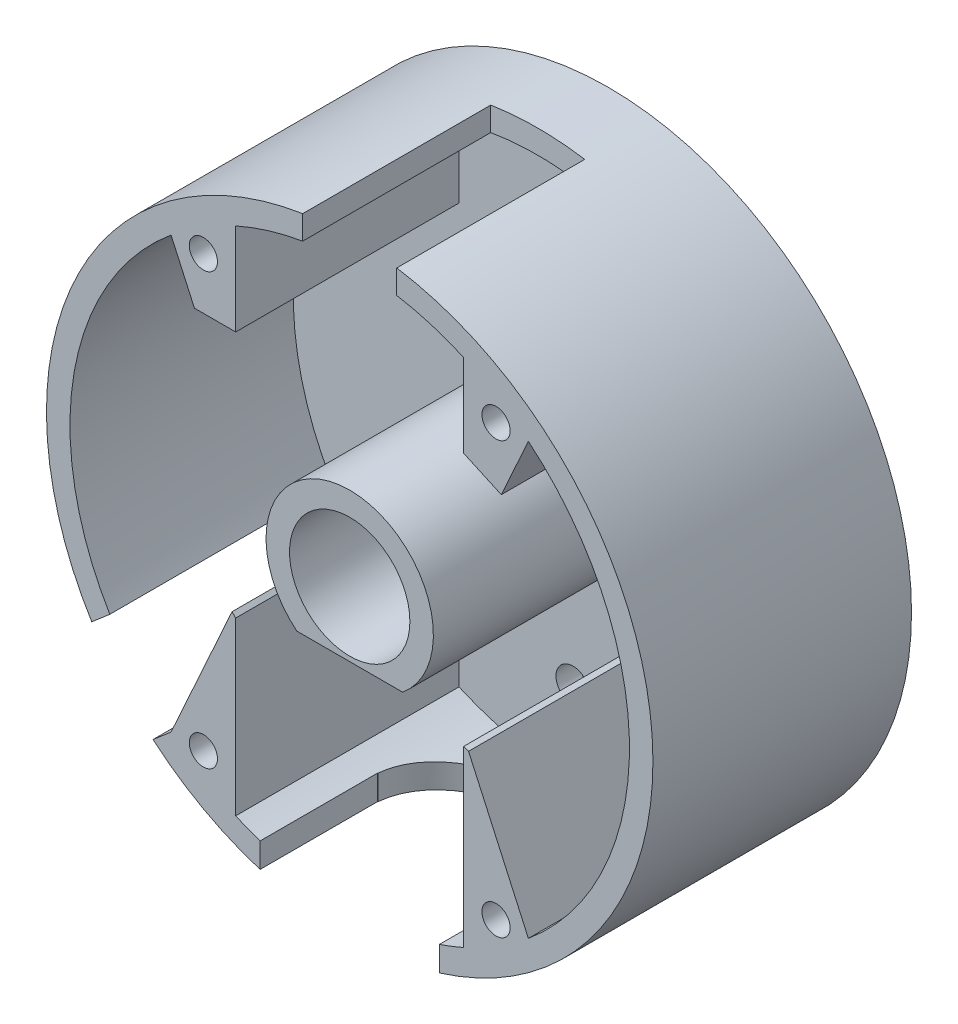
SolidWorks part; units mm, degrees
ref_plane "前视基准面" through (0, 0, 0) normal (0, 0, 1) x (1, 0, 0)
ref_plane "上视基准面" through (0, 0, 0) normal (0, 1, 0) x (1, 0, 0)
ref_plane "右视基准面" through (0, 0, 0) normal (1, 0, 0) x (0, 0, -1)
other "Configuration Table"
sketch "草图1" plane through (0, 0, 0) normal (0, 0, 1) x (1, 0, 0)
  line L4 (3, -31.3615) -> (93, -31.3615)
  line L5 (93, -31.3615) -> (93, 31.3615)
  line L6 (93, 31.3615) -> (3, 31.3615)
  line L7 (3, 31.3615) -> (3, -31.3615)
  line L8 (3, -31.3615) -> (93, -31.3615)
  line L9 (93, -31.3615) -> (93, 31.3615)
  line L10 (93, 31.3615) -> (3, 31.3615)
  line L11 (3, 31.3615) -> (3, -31.3615)
  circle A0 centre (64, 0) radius 5 construction
  circle A1 centre (64, 0) radius 5
  arc A2 (64, -25.8) -> (64, 25.8) centre (64, 0) ccw construction
  arc A3 (64, -25.8) -> (64, 25.8) centre (64, 0) ccw
  circle A4 centre (64, 0) radius 25.8
  dimension "D1" = 0
extrude "凸台-拉伸1" add sketch "草图1" along normal blind 2 contours A3 A4 A1 region at (38.9297, 0, 0)
sketch "草图2" plane through (0, 0, 2) normal (0, 0, 1) x (1, 0, 0)
  circle A1 centre (64, 0) radius 25.8
  circle A2 centre (64, 0) radius 25.8
  circle A3 centre (64, 0) radius 23.8
  dimension "D1" = 0
  dimension "D3" = 2
extrude "凸台-拉伸2" add sketch "草图2" against normal up to surface (2 mm away) and the other way blind 20 up to face at (69, 0, 0)
sketch "草图3" plane through (0, 0, 2) normal (0, 0, 1) x (1, 0, 0)
  line L1 (64, -23.8) -> (64, -16.8)
  line L2 (64, -15.35) -> (64, -23.8)
  circle A0 centre (64, 0) radius 5 construction
  circle A1 centre (64, 0) radius 23.8
  circle A3 centre (64, 0) radius 5
  circle A6 centre (64, -16.8) radius 1.45
  circle A8 centre (64, 0) radius 23.8
  dimension "D3" = 2.9
  dimension "D1" = 0
extrude "切除-拉伸2" cut sketch "草图3" against normal up to surface (2 mm away) contours A6 | A6 region at (63.3846, -16.8, 2) region at (64.6154, -16.8, 2) up to face at (89.8, 0, 0)
sketch "草图4" plane through (0, 0, 2) normal (0, 0, 1) x (1, 0, 0)
  circle A0 centre (64, -16.8) radius 1.45 construction
  circle A1 centre (64, 0) radius 23.8
  circle A3 centre (64, -16.8) radius 1.45
  circle A5 centre (64, 0) radius 23.8
  dimension "D1" = 0
extrude "凸台-拉伸3" add sketch "草图4" along normal blind 1 contours A5 | A3
sketch "草图5" plane through (0, 0, 0) normal (0, 0, -1) x (-1, 0, 0)
  circle A0 centre (-64, -16.8) radius 1.45 construction
  circle A1 centre (-64, 0) radius 25.8
  circle A3 centre (-64, -16.8) radius 1.45
  circle A4 centre (-64, -16.8) radius 3.05
  circle A6 centre (-64, 0) radius 25.8
  circle M2 centre (-64, -16.8) radius 1.45
  dimension "D1" = 0
  dimension "D2" = 1.6
extrude "切除-拉伸3" cut sketch "草图5" against normal blind 1 contours A4 M2 region at (66.9637, -16.8, 0)
sketch "草图6" plane through (74.5, -5.45, -15.2) normal (0, 1, 0) x (0, 0, -1)
  line L0 (-18.2, 20) -> (-37.2, 20) construction
  line L1 (-18.2, 20) -> (-37.2, 20)
  circle A2 centre (-27.7, 10.5) radius 7.625
extrude "切除-拉伸5" cut sketch "草图6" against normal up to surface (19.1975 mm away) contours A2 up to face at (89.8, 0, 0)
sketch "草图7" plane through (0, 0, 22) normal (0, 0, 1) x (1, 0, 0)
  line L0 (64, 0) -> (44.4194, -16.8)
  line L1 (64, 0) -> (64, 25.8)
  line L2 (68, -1.8386) -> (47.024, -19.8358)
  line L3 (68, -1.8386) -> (68, 25.8)
  line L4 (60, 1.8386) -> (41.8147, -13.7642)
  line L5 (60, 1.8386) -> (60, 25.8)
  circle A0 centre (64, 0) radius 23.8 construction
  circle A1 centre (64, 0) radius 25.8
  circle A2 centre (64, 0) radius 25.8
  circle A3 centre (64, 0) radius 23.8
  circle A4 centre (64, -16.8) radius 1.45 construction
  circle A5 centre (64, 0) radius 23.8
  circle A6 centre (64, 0) radius 23.8
  circle A7 centre (64, -16.8) radius 1.45
  circle A8 centre (64, 0) radius 5
  circle M6 centre (64, 0) radius 25.8
  circle M7 centre (64, 0) radius 23.8
  dimension "D1" = 0
  dimension "D2" = 0
  dimension "D3" = 4
  dimension "D4" = 4
extrude "切除-拉伸6" cut sketch "草图7" against normal blind 16 contours L2 L0 M7 M6 | L4 L0 M7 M6 | L3 L1 M7 M6 | L5 L1 M7 M6 region at (46.5659, -17.5994, 22) region at (43.9555, -14.557, 22) region at (61.9956, 24.6915, 22) region at (66.0044, 24.6915, 22)
sketch "草图8" plane through (0, 0, 3) normal (0, 0, 1) x (1, 0, 0)
  line L0 (54.5, -6.16) -> (54.5, -20.16) construction
  line L1 (54.5, -6.16) -> (54.5, -20.16)
  line L2 (73.5, -6.16) -> (73.5, -20.16) construction
  line L3 (73.5, -6.16) -> (73.5, -20.16)
  line L4 (54.3, -6.16) -> (54.3, -20.16)
  line L5 (73.7, -6.16) -> (73.7, -20.16)
  line L6 (54.3, -20.16) -> (54.3, -21.7336)
  line L7 (73.7, -20.16) -> (73.7, -21.7336)
  line L8 (54.5, -20.16) -> (73.5, -20.16)
  line L9 (73.5, -20.16) -> (73.5, -6.16)
  line L10 (73.5, -6.16) -> (54.5, -6.16)
  line L11 (54.5, -6.16) -> (54.5, -20.16)
  line L12 (54.5, -20.16) -> (73.5, -20.16)
  line L13 (73.5, -20.16) -> (73.5, -6.16)
  line L14 (73.5, -6.16) -> (54.5, -6.16)
  line L15 (54.5, -6.16) -> (54.5, -20.16)
  line L16 (73.7, -6.16) -> (79.2011, -18.313)
  line L18 (48.7989, -18.313) -> (54.3, -6.16)
  circle A1 centre (64, 0) radius 23.8
  circle A2 centre (64, 0) radius 23.8
  circle M9 centre (64, 0) radius 23.8
  dimension "D1" = 0
  dimension "D2" = 0
  dimension "D3" = 0.2
  dimension "D4" = 0.2
extrude "凸台-拉伸5" add sketch "草图8" along normal up to surface (19 mm away) contours L16 L5 L7 M9 | L18 L6 L4 M9 region at (52.4452, -15.5048, 3) region at (75.5548, -15.5048, 3) up to face at (72.2743, -3.8032, 22)
chamfer "倒角1" distance 1 angle 45 2 edges at (54.3, -6.16, 12.5) (73.7, -6.16, 12.5) first distance on face at (54.3, -13.9468, 12.5) first distance on face at (76.4506, -12.2365, 12.5)
sketch "草图9" plane through (0, 0, 3) normal (0, 0, 1) x (1, 0, 0)
  line L1 (59.5029, -5.52) -> (68.4971, -5.52)
  line L2 (64, -7.12) -> (64, -5.52)
  line L6 (48.7989, -18.313) -> (53.9884, -6.8484)
  line L7 (53.9884, -6.8484) -> (54.3, -7.16)
  line L8 (54.3, -7.16) -> (54.3, -21.7336)
  line L9 (73.7, -21.7336) -> (73.7, -6.9156)
  line L10 (73.7, -6.9156) -> (74.1124, -7.071)
  line L11 (74.1124, -7.071) -> (79.2011, -18.313)
  line L12 (48.7989, -18.313) -> (53.9884, -6.8484)
  line L13 (53.9884, -6.8484) -> (54.3, -7.16)
  line L14 (54.3, -7.16) -> (54.3, -21.7336)
  line L15 (73.7, -21.7336) -> (73.7, -6.9156)
  line L16 (73.7, -6.9156) -> (74.1124, -7.071)
  line L17 (74.1124, -7.071) -> (79.2011, -18.313)
  circle A0 centre (64, 0) radius 5 construction
  circle A1 centre (64, 0) radius 5
  arc A2 (54.3, -21.7336) -> (73.7, -21.7336) centre (64, 0) ccw
  arc A3 (79.2011, -18.313) -> (48.7989, -18.313) centre (64, 0) ccw
  arc A4 (54.3, -21.7336) -> (73.7, -21.7336) centre (64, 0) ccw
  arc A5 (79.2011, -18.313) -> (48.7989, -18.313) centre (64, 0) ccw
  circle A6 centre (64, 0) radius 5.12
  circle A7 centre (64, 0) radius 7.12
  dimension "D2" = 0.12
  dimension "D4" = 1.6
  dimension "D1" = 0
  dimension "D3" = 2
extrude "凸台-拉伸6" add sketch "草图9" along normal up to surface (19 mm away) contours L1 A7 A6 region at (61.026, 6.259, 3) up to face at (46.4383, 8.072, 22)
sketch "草图11" plane through (0, 0, 22) normal (0, 0, 1) x (1, 0, 0)
  line L0 (64, 0) -> (87.8, 0)
  line L1 (79.2011, -18.313) -> (73.7, -18.313)
  line L2 (64, 0) -> (64, -23.8)
  line L3 (73.7, 6.9156) -> (73.7, 21.7336)
  line L4 (74.1124, 7.071) -> (73.7, 6.9156)
  line L5 (79.2011, 18.313) -> (74.1124, 7.071)
  line L6 (68, -25.488) -> (68, -23.4615)
  line L7 (48.7989, 18.313) -> (47.2608, 19.6326)
  line L8 (54.3, -21.7336) -> (54.3, -7.16)
  line L9 (54.3, -7.16) -> (53.9884, -6.8484)
  line L10 (53.9884, -6.8484) -> (48.7989, -18.313)
  line L11 (48.7989, -18.313) -> (47.2608, -19.6326)
  line L12 (68, 25.488) -> (68, 23.4615)
  line L13 (79.2011, -18.313) -> (74.1124, -7.071)
  line L14 (74.1124, -7.071) -> (73.7, -6.9156)
  line L15 (73.7, -6.9156) -> (73.7, -21.7336)
  line L16 (54.3, -21.7336) -> (54.3, -7.16)
  line L17 (54.3, -7.16) -> (53.9884, -6.8484)
  line L18 (53.9884, -6.8484) -> (48.7989, -18.313)
  line L19 (48.7989, -18.313) -> (47.2608, -19.6326)
  line L20 (68, 25.488) -> (68, 23.4615)
  line L21 (79.2011, -18.313) -> (74.1124, -7.071)
  line L22 (74.1124, -7.071) -> (73.7, -6.9156)
  line L23 (73.7, -6.9156) -> (73.7, -21.7336)
  line L24 (53.9884, 6.8484) -> (48.7989, 18.313)
  line L25 (54.3, 7.16) -> (53.9884, 6.8484)
  line L26 (54.3, 21.7336) -> (54.3, 7.16)
  circle A0 centre (64, 0) radius 23.8
  circle A1 centre (76.4506, -18.313) radius 1.2
  circle A2 centre (51.5494, -18.313) radius 1.2
  arc A3 (47.2608, -19.6326) -> (68, 25.488) centre (64, 0) ccw
  arc A4 (79.2011, -18.313) -> (68, 23.4615) centre (64, 0) ccw
  arc A5 (54.3, -21.7336) -> (73.7, -21.7336) centre (64, 0) ccw
  arc A6 (47.2608, -19.6326) -> (68, 25.488) centre (64, 0) ccw
  arc A7 (79.2011, -18.313) -> (68, 23.4615) centre (64, 0) ccw
  arc A8 (54.3, -21.7336) -> (73.7, -21.7336) centre (64, 0) ccw
  arc A9 (54.3, 21.7336) -> (73.7, 21.7336) centre (64, 0) cw
  arc A10 (79.2011, 18.313) -> (68, -23.4615) centre (64, 0) cw
  arc A11 (47.2608, 19.6326) -> (68, -25.488) centre (64, 0) cw
  circle A12 centre (51.5494, 18.313) radius 1.2
  circle A13 centre (76.4506, 18.313) radius 1.2
  arc M22 (68, 23.4615) -> (79.2011, -18.313) centre (64, 0) cw
  dimension "D2" = 2.4
  dimension "D1" = 0
extrude "凸台-拉伸7" add sketch "草图11" against normal up to surface (19 mm away) contours L5 L3 L4 A13 M22 | L26 A0 L24 L25 A12 region at (75.458, 15.2151, 22) region at (52.5419, 15.215, 22) up to face at (64, 0.8, 3)
chamfer "倒角3" distance 10 angle 45 2 edges at (53.9884, 6.8484, 12.5) (73.7, 6.9156, 12.5) first distance on face at (54.1442, 7.0042, 12.5) first distance on face at (73.9062, 6.9933, 12.5)
sketch "草图13" plane through (0, 0, 22) normal (0, 0, 1) x (1, 0, 0)
  line L11 (73.7, 21.7336) -> (73.7, 14.6774)
  line L12 (73.7, 14.6774) -> (76.8998, 13.229)
  line L13 (76.8998, 13.229) -> (79.2011, 18.313)
  line L14 (79.2011, -18.313) -> (74.1124, -7.071)
  line L15 (74.1124, -7.071) -> (73.7, -6.9156)
  line L16 (73.7, -6.9156) -> (73.7, -21.7336)
  line L17 (54.3, -21.7336) -> (54.3, -7.16)
  line L18 (54.3, -7.16) -> (53.9884, -6.8484)
  line L19 (53.9884, -6.8484) -> (48.7989, -18.313)
  line L20 (48.7989, -18.313) -> (47.2608, -19.6326)
  line L21 (68, 25.488) -> (68, 23.4615)
  line L22 (73.7, 21.7336) -> (73.7, 14.6774)
  line L23 (73.7, 14.6774) -> (76.8998, 13.229)
  line L24 (76.8998, 13.229) -> (79.2011, 18.313)
  line L25 (79.2011, -18.313) -> (74.1124, -7.071)
  line L26 (74.1124, -7.071) -> (73.7, -6.9156)
  line L27 (73.7, -6.9156) -> (73.7, -21.7336)
  line L28 (54.3, -21.7336) -> (54.3, -7.16)
  line L29 (54.3, -7.16) -> (53.9884, -6.8484)
  line L30 (53.9884, -6.8484) -> (48.7989, -18.313)
  line L31 (48.7989, -18.313) -> (47.2608, -19.6326)
  line L32 (68, 25.488) -> (68, 23.4615)
  circle A0 centre (76.4506, -18.313) radius 1.2 construction
  circle A1 centre (76.4506, -18.313) radius 1.2
  circle A2 centre (51.5494, -18.313) radius 1.2 construction
  circle A3 centre (51.5494, -18.313) radius 1.2
  arc A4 (79.2011, -18.313) -> (79.2011, 18.313) centre (64, 0) ccw
  arc A5 (54.3, -21.7336) -> (73.7, -21.7336) centre (64, 0) ccw
  arc A6 (47.2608, -19.6326) -> (68, 25.488) centre (64, 0) ccw
  arc A7 (73.7, 21.7336) -> (68, 23.4615) centre (64, 0) ccw
  arc A8 (79.2011, -18.313) -> (79.2011, 18.313) centre (64, 0) ccw
  arc A9 (54.3, -21.7336) -> (73.7, -21.7336) centre (64, 0) ccw
  arc A10 (47.2608, -19.6326) -> (68, 25.488) centre (64, 0) ccw
  arc A11 (73.7, 21.7336) -> (68, 23.4615) centre (64, 0) ccw
  dimension "D1" = 0
extrude "切除-拉伸7" cut sketch "草图13" against normal up to surface (19 mm away) contours A3 | A1 up to face at (65.45, -16.8, 3)
sketch "草图14" plane through (0, 0, 22) normal (0, 0, 1) x (1, 0, 0)
  line L0 (56.375, -24.6475) -> (56.375, -22.5455)
  line L1 (71.625, -24.6475) -> (71.625, -22.5455)
  line L11 (73.7, 21.7336) -> (73.7, 14.6774)
  line L12 (73.7, 14.6774) -> (76.8998, 13.229)
  line L13 (76.8998, 13.229) -> (79.2011, 18.313)
  line L14 (79.2011, -18.313) -> (74.1124, -7.071)
  line L15 (74.1124, -7.071) -> (73.7, -6.9156)
  line L16 (73.7, -6.9156) -> (73.7, -21.7336)
  line L17 (54.3, -21.7336) -> (54.3, -7.16)
  line L18 (54.3, -7.16) -> (53.9884, -6.8484)
  line L19 (53.9884, -6.8484) -> (48.7989, -18.313)
  line L20 (48.7989, -18.313) -> (47.2608, -19.6326)
  line L21 (68, 25.488) -> (68, 23.4615)
  line L22 (73.7, 21.7336) -> (73.7, 14.6774)
  line L23 (73.7, 14.6774) -> (76.8998, 13.229)
  line L24 (76.8998, 13.229) -> (79.2011, 18.313)
  line L25 (79.2011, -18.313) -> (74.1124, -7.071)
  line L26 (74.1124, -7.071) -> (73.7, -6.9156)
  line L27 (73.7, -6.9156) -> (73.7, -21.7336)
  line L28 (54.3, -21.7336) -> (54.3, -7.16)
  line L29 (54.3, -7.16) -> (53.9884, -6.8484)
  line L30 (53.9884, -6.8484) -> (48.7989, -18.313)
  line L31 (48.7989, -18.313) -> (47.2608, -19.6326)
  line L32 (68, 25.488) -> (68, 23.4615)
  arc A0 (56.375, -24.6475) -> (71.625, -24.6475) centre (64, 0) ccw construction
  arc A1 (56.375, -24.6475) -> (71.625, -24.6475) centre (64, 0) ccw
  arc A4 (79.2011, -18.313) -> (79.2011, 18.313) centre (64, 0) ccw
  arc A5 (54.3, -21.7336) -> (73.7, -21.7336) centre (64, 0) ccw
  arc A6 (47.2608, -19.6326) -> (68, 25.488) centre (64, 0) ccw
  arc A7 (73.7, 21.7336) -> (68, 23.4615) centre (64, 0) ccw
  arc A8 (79.2011, -18.313) -> (79.2011, 18.313) centre (64, 0) ccw
  arc A9 (54.3, -21.7336) -> (73.7, -21.7336) centre (64, 0) ccw
  arc A10 (47.2608, -19.6326) -> (68, 25.488) centre (64, 0) ccw
  arc A11 (73.7, 21.7336) -> (68, 23.4615) centre (64, 0) ccw
  arc M25 (73.7, -21.7336) -> (54.3, -21.7336) centre (64, 0) cw
  arc M30 (47.2608, -19.6326) -> (68, 25.488) centre (64, 0) ccw
  dimension "D1" = 0
extrude "切除-拉伸8" cut sketch "草图14" against normal blind 10 contours L1 L0 M30 M25 region at (64, -24.3975, 22)
sketch "草图15" plane through (0, 0, 3) normal (0, 0, 1) x (1, 0, 0)
  circle A1 centre (64, 0) radius 5.12
  circle A2 centre (64, 0) radius 5.12
  dimension "D1" = 0
extrude "切除-拉伸9" cut sketch "草图15" against normal blind 10
